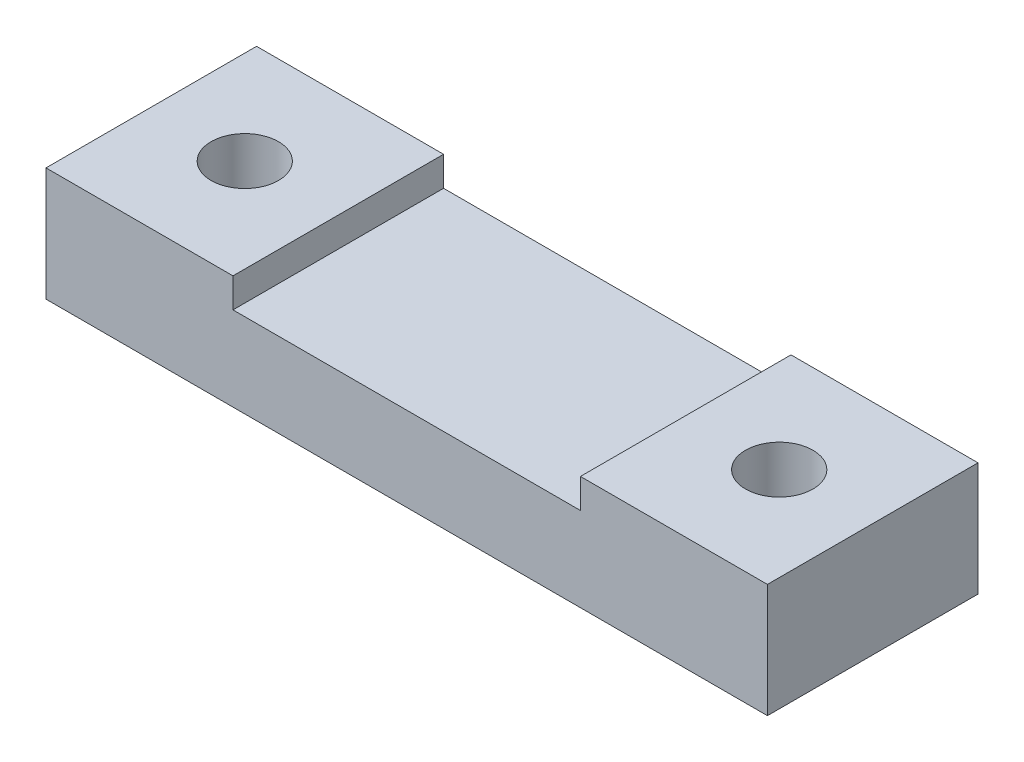
SolidWorks part; units mm, degrees
ref_plane "Front Plane" through (0, 0, 0) normal (0, 0, 1) x (1, 0, 0)
ref_plane "Top Plane" through (0, 0, 0) normal (0, 1, 0) x (1, 0, 0)
ref_plane "Right Plane" through (0, 0, 0) normal (1, 0, 0) x (0, 0, -1)
sketch "Sketch1" plane through (0, 0, 0) normal (0, 1, 0) x (1, 0, 0)
  line L0 (0, 5) -> (8.88, 5)
  line L1 (0, 0) -> (34.26, 0)
  line L2 (0, 0) -> (0, 10)
  line L3 (0, 10) -> (34.26, 10)
  line L4 (34.26, 0) -> (34.26, 10)
  line L5 (8.88, 5) -> (8.88, 10)
  line L6 (8.88, 10) -> (8.88, 5)
  line L7 (8.88, 5) -> (8.88, 0)
  line L8 (8.88, 5) -> (25.38, 5)
  line L9 (25.38, 5) -> (34.26, 5)
  line L10 (25.38, 5) -> (25.38, 10)
  line L11 (25.38, 10) -> (25.38, 0)
  circle A0 centre (4.44, 5) radius 1.6
  circle A1 centre (29.82, 5) radius 1.6
extrude "Boss-Extrude1" add sketch "Sketch1" along normal blind 1.4 contours L7 L0 L2 L1 | L0 L5 L3 L2 | L9 L11 L1 L4 | L10 L9 L4 L3 region at (4.44, 0, -7.6813) region at (4.44, 0, -2.3187) region at (29.82, 0, -7.6813) region at (29.82, 0, -2.3187)
extrude "Boss-Extrude3" add sketch "Sketch1<5>" against normal blind 4 contours L11 L8 L7 L1 | L8 L10 L3 L5 | L9 L11 L1 L4 | L10 L9 L4 L3 | L7 L0 L2 L1 | L0 L5 L3 L2 region at (4.44, 0, -7.6813) region at (4.44, 0, -2.3187) region at (17.13, 0, -2.5) region at (17.13, 0, -7.5) region at (29.82, 0, -7.6813) region at (29.82, 0, -2.3187)
sketch "Sketch1<5>" plane through (0, 0, 0) normal (0, 1, 0) x (1, 0, 0) same geometry as "Sketch1"
